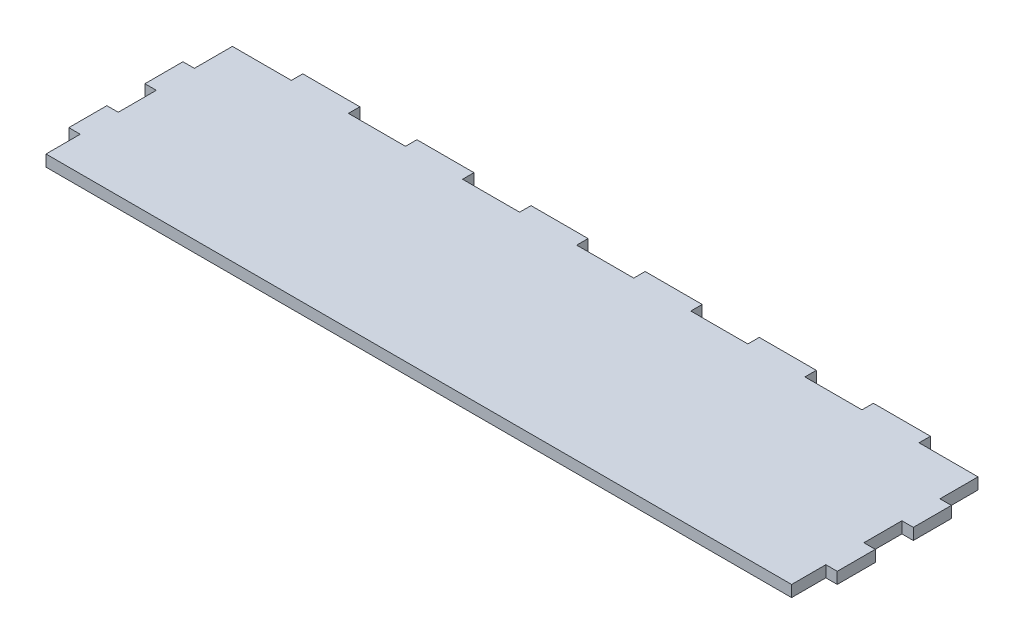
SolidWorks part; units mm, degrees
ref_plane "Front Plane" through (0, 0, 0) normal (0, 0, 1) x (1, 0, 0)
ref_plane "Top Plane" through (0, 0, 0) normal (0, 1, 0) x (1, 0, 0)
ref_plane "Right Plane" through (0, 0, 0) normal (1, 0, 0) x (0, 0, -1)
sketch "Sketch1" plane through (0, 0, 0) normal (0, 1, 0) x (1, 0, 0)
  line L0 (15, 0) -> (-0.5, 0)
  line L1 (15, 0) -> (15, 3)
  line L2 (15, 3) -> (30, 3)
  line L3 (30, 3) -> (30, 0)
  line L4 (30, 0) -> (45, 0)
  line L5 (45, 0) -> (45, 3)
  line L6 (45, 3) -> (60, 3)
  line L7 (60, 3) -> (60, 0)
  line L8 (60, 0) -> (75, 0)
  line L9 (75, 0) -> (75, 3)
  line L10 (75, 3) -> (90, 3)
  line L11 (90, 3) -> (90, 0)
  line L12 (90, 0) -> (105, 0)
  line L13 (105, 0) -> (105, 3)
  line L14 (105, 3) -> (120, 3)
  line L15 (120, 3) -> (120, 0)
  line L16 (120, 0) -> (135, 0)
  line L17 (135, 0) -> (135, 3)
  line L18 (135, 3) -> (150, 3)
  line L19 (150, 3) -> (150, 0)
  line L20 (150, 0) -> (165, 0)
  line L21 (165, 0) -> (165, 3)
  line L22 (165, 3) -> (180, 3)
  line L23 (180, 3) -> (180, 0)
  line L24 (180, 0) -> (195.5, 0)
  line L25 (-0.5, 0) -> (-0.5, -10)
  line L26 (-0.5, -10) -> (-3.5, -10)
  line L27 (-3.5, -10) -> (-3.5, -20)
  line L28 (-3.5, -20) -> (-0.5, -20)
  line L29 (-0.5, -20) -> (-0.5, -30)
  line L30 (-0.5, -30) -> (-3.5, -30)
  line L31 (-3.5, -30) -> (-3.5, -40)
  line L32 (-3.5, -40) -> (-0.5, -40)
  line L33 (-0.5, -40) -> (-0.5, -49)
  line L34 (-0.5, -49) -> (195.5, -49)
  line L35 (97.5, 0) -> (97.5, -49) construction
  line L36 (195.5, -40) -> (195.5, -49)
  line L37 (198.5, -40) -> (195.5, -40)
  line L38 (198.5, -30) -> (198.5, -40)
  line L39 (195.5, -30) -> (198.5, -30)
  line L40 (195.5, -20) -> (195.5, -30)
  line L41 (198.5, -20) -> (195.5, -20)
  line L42 (198.5, -10) -> (198.5, -20)
  line L43 (195.5, -10) -> (198.5, -10)
  line L44 (195.5, 0) -> (195.5, -10)
  dimension "D1" = 6
  dimension "D2" = 15
  dimension "D3" = 3
  dimension "D4" = 3
  dimension "D6" = 15.5
  dimension "D7" = 10
  dimension "D8" = 10
  dimension "D9" = 3
  dimension "D10" = 10
  dimension "D11" = 10
  dimension "D12" = 9
extrude "Boss-Extrude1" add sketch "Sketch1" along normal blind 3
